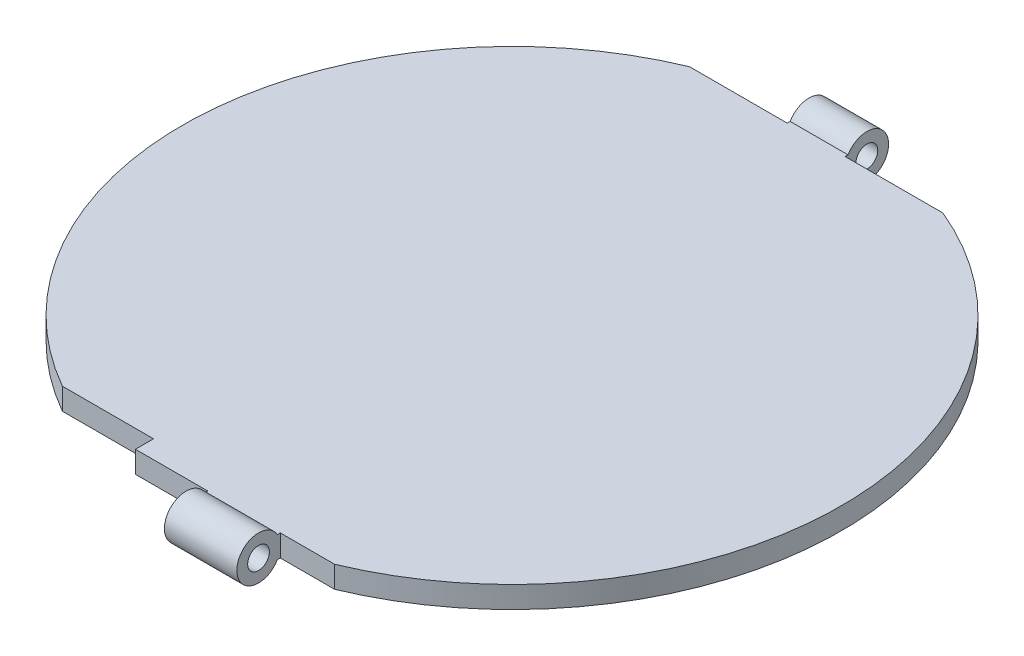
SolidWorks part; units mm, degrees
ref_plane "Front Plane" through (0, 0, 0) normal (0, 0, 1) x (1, 0, 0)
ref_plane "Top Plane" through (0, 0, 0) normal (0, 1, 0) x (1, 0, 0)
ref_plane "Right Plane" through (0, 0, 0) normal (1, 0, 0) x (0, 0, -1)
sketch "Sketch1" plane through (0, 0, 0) normal (0, 1, 0) x (1, 0, 0)
  line L0 (-17.5, -42) -> (17.5, -42)
  line L1 (0, 0) -> (36.3754, 0) construction
  line L2 (-17.5, 42) -> (17.5, 42)
  arc A0 (-17.5, 42) -> (-17.5, -42) centre (0, 0) ccw
  arc A1 (17.5, -42) -> (17.5, 42) centre (0, 0) ccw
  point P8 (36.3754, 0)
  dimension "D1" = 91
  dimension "D2" = 42
  dimension "D3" = 42
extrude "Boss-Extrude1" add sketch "Sketch1" along normal blind 3
sketch "Sketch2" plane through (0, 0, 0) normal (1, 0, 0) x (0, 0, -1)
  line L0 (-43.0566, 1.5) -> (50.2125, 1.5) construction
  line L1 (-42, 3) -> (-42, 0) construction
  line L2 (-42, 0) -> (-42.4019, 0)
  line L3 (-42, 0) -> (42, 0) construction
  line L4 (-42, 0) -> (-42, 1.5)
  line L5 (-42, 1.5) -> (-42, 3)
  line L6 (-42, 3) -> (-42.4019, 3)
  line L7 (42, 3) -> (-42, 3) construction
  circle A0 centre (-45, 1.5) radius 1.5
  arc A1 (-42.4019, 3) -> (-42.4019, 0) centre (-45, 1.5) ccw
  point P4 (-42, 1.5)
  point P8 (-42.312, 3.2155)
  dimension "D1" = 6
  dimension "D2" = 3
extrude "Boss-Extrude2" add sketch "Sketch2" along normal blind 10 and the other way blind 10
mirror "Mirror1" about plane through (0, 0, 0) normal (0, 0, 1) of "Boss-Extrude2"
sketch "Sketch3" plane through (-10, 0, 0) normal (-1, 0, 0) x (0, 0, 1)
  line L0 (42, 0) -> (42, 3) construction
  line L1 (42, 6.5) -> (50, 6.5)
  line L2 (42, 6.5) -> (42, -2.5)
  line L3 (42, -2.5) -> (50, -2.5)
  line L4 (50, 6.5) -> (50, -2.5)
  circle A0 centre (45, 1.5) radius 1.5 construction
  dimension "D1" = 9
  dimension "D2" = 8
  dimension "D3" = 5
extrude "Cut-Extrude1" cut sketch "Sketch3" against normal blind 10
sketch "Sketch4" plane through (-10, 0, 0) normal (-1, 0, 0) x (0, 0, 1)
  line L5 (-42, 0) -> (-42, 3) construction
  line L6 (-42, -2.5) -> (-50, -2.5)
  line L7 (-42, -2.5) -> (-42, 6.5)
  line L8 (-42, 6.5) -> (-50, 6.5)
  line L10 (-50, 6.5) -> (-50, -2.5)
  circle A0 centre (-45, 1.5) radius 1.5 construction
  dimension "D1" = 8
  dimension "D2" = 9
  dimension "D3" = 5
extrude "Cut-Extrude2" cut sketch "Sketch4" against normal blind 6
mirror "Mirror2" about plane through (0, 0, 0) normal (1, 0, 0) of "Cut-Extrude2"
ref_plane "Plane1" through (-10, 0, 0) normal (-1, 0, 0) x (0, 0, 1)
sketch "Sketch5" plane through (-10, 0, 0) normal (-1, 0, 0) x (0, 0, 1)
  line L0 (45, 1.5) -> (46.1591, 1.5) construction
  line L1 (39.5, -4.5) -> (50.5, -4.5)
  line L2 (39.5, -4.5) -> (39.5, 7.5)
  line L3 (39.5, 7.5) -> (50.5, 7.5)
  line L4 (50.5, -4.5) -> (50.5, 7.5)
  line L5 (45, 1.5) -> (45, 2.4658) construction
  point P5 (45, 7.5)
  point P9 (50.5, 1.5)
  dimension "D1" = 11
  dimension "D2" = 12
extrude "Cut-Extrude3" cut sketch "Sketch5" along normal up to surface (12.5832 mm away) up to face at (-31.5, 1.5, 0)
